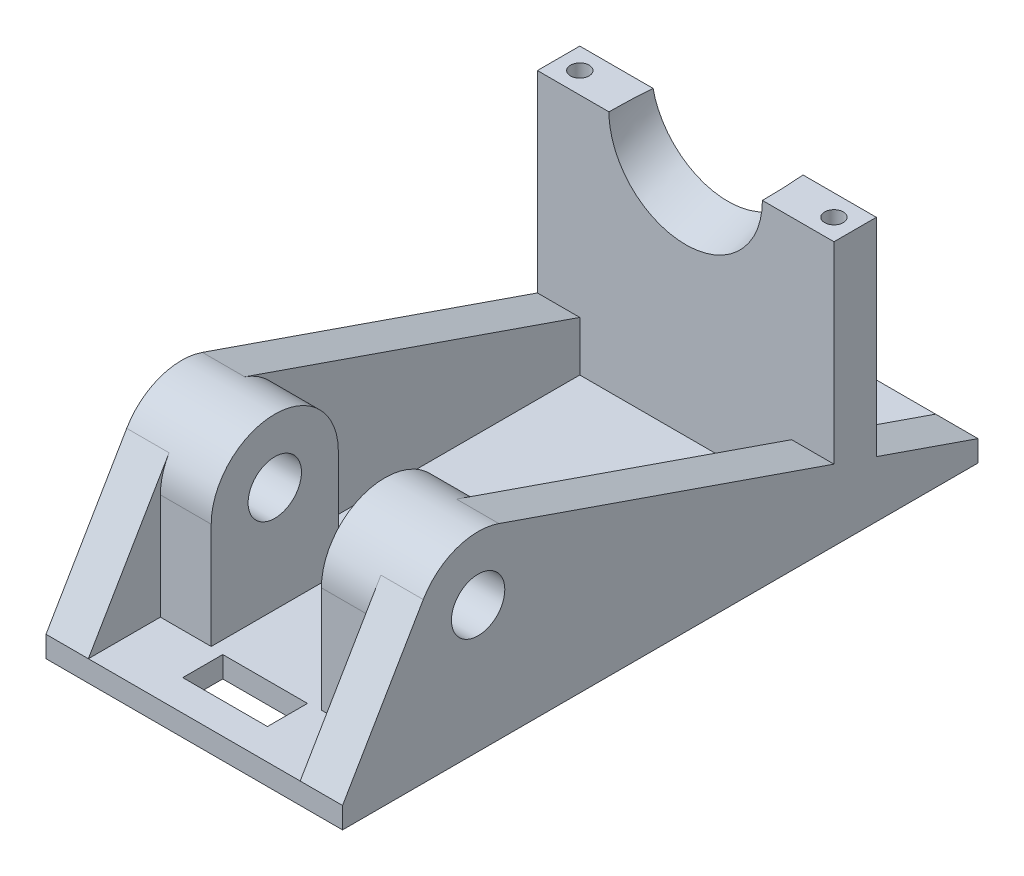
SolidWorks part; units mm, degrees
ref_plane "Front Plane" through (0, 0, 0) normal (0, 0, 1) x (1, 0, 0)
ref_plane "Top Plane" through (0, 0, 0) normal (0, 1, 0) x (1, 0, 0)
ref_plane "Right Plane" through (0, 0, 0) normal (1, 0, 0) x (0, 0, -1)
sketch "Sketch1" plane through (0, 0, 0) normal (0, 1, 0) x (1, 0, 0)
  line L1 (22.225, -47.625) -> (-22.225, -47.625)
  line L2 (22.225, -47.625) -> (22.225, 47.625)
  line L3 (22.225, 47.625) -> (-22.225, 47.625)
  line L4 (-22.225, -47.625) -> (-22.225, 47.625)
  line L5 (22.225, -47.625) -> (-22.225, 47.625) construction
  line L6 (22.225, 47.625) -> (-22.225, -47.625) construction
  point P0 (0, 0)
  dimension "D1" = 95.25
  dimension "D2" = 44.45
extrude "Boss-Extrude1" add sketch "Sketch1" along normal blind 3.175
sketch "Sketch2" plane through (0, 0, 0) normal (1, 0, 0) x (0, 0, -1)
  line L3 (-47.625, 3.175) -> (-47.625, 0) construction
  line L4 (-36.83, 3.175) -> (-36.83, 19.05)
  line L5 (-24.1873, 28.0503) -> (47.625, 3.175)
  line L6 (-47.625, 3.175) -> (47.625, 3.175)
  line L7 (-47.625, 3.175) -> (-35.5269, 23.859)
  line L8 (-17.78, 3.175) -> (-17.78, 19.05)
  circle A0 centre (-27.305, 19.05) radius 4
  arc A2 (-35.5269, 23.859) -> (-24.1873, 28.0503) centre (-27.305, 19.05) cw
  arc A3 (-17.78, 19.05) -> (-36.83, 19.05) centre (-27.305, 19.05) ccw
  point P6 (-47.625, 1.5875)
  dimension "D1" = 8
  dimension "D6" = 19.05
  dimension "D2" = 20.32
  dimension "D3" = 19.05
extrude "Boss-Extrude2" add sketch "Sketch2" along normal mid plane 44.45 contours A2 L6 L5 | A2 A0 | A3 L7 L6 L4 region at (0, 9.3974, 40.4061) region at (0, 14.4275, 27.305) region at (0, 10.8864, -3.7601)
extrude "Cut-Extrude1" cut sketch "Sketch2<3>" against normal mid plane 31.75 contours A3 L7 L6 L4 | A3 L8 L6 L5 region at (0, 9.3974, 40.4061) region at (0, 10.8864, -3.7601)
sketch "Sketch2<3>" plane through (0, 0, 0) normal (1, 0, 0) x (0, 0, -1) same geometry as "Sketch2"
extrude "Cut-Extrude2" cut sketch "Sketch2<4>" against normal mid plane 16.51 contours A2 A0 | A0 region at (0, 14.4275, 27.305) region at (0, 19.05, 27.305)
sketch "Sketch2<4>" plane through (0, 0, 0) normal (1, 0, 0) x (0, 0, -1) same geometry as "Sketch2"
sketch "Sketch3" plane through (0, 3.175, 0) normal (0, 1, 0) x (1, 0, 0)
  line L0 (-15.875, 0) -> (15.875, 0) construction
  line L5 (-15.875, -24.1873) -> (-15.875, 47.625) construction
  line L6 (15.875, -17.78) -> (15.875, 47.625) construction
  line L8 (-6.35, 43.005) -> (6.35, 43.005)
  line L9 (-6.35, 43.005) -> (-6.35, 37.005)
  line L10 (-6.35, 37.005) -> (6.35, 37.005)
  line L11 (6.35, 43.005) -> (6.35, 37.005)
  line L12 (-6.35, 43.005) -> (6.35, 37.005) construction
  line L13 (6.35, 43.005) -> (-6.35, 37.005) construction
  line L14 (-15.875, 47.625) -> (15.875, 47.625) construction
  line L15 (-6.35, -37.005) -> (6.35, -37.005)
  line L16 (6.35, -43.005) -> (6.35, -37.005)
  line L17 (-6.35, -43.005) -> (6.35, -43.005)
  line L18 (-6.35, -43.005) -> (-6.35, -37.005)
  point P11 (0, 37.005)
  point P12 (0, 40.005)
  dimension "D1" = 12.7
  dimension "D2" = 6
  dimension "D3" = 7.62
extrude "Cut-Extrude3" cut sketch "Sketch3" against normal through all
sketch "Sketch4" plane through (0, 3.175, 0) normal (0, 1, 0) x (1, 0, 0)
  line L0 (-22.225, -24.1873) -> (-22.225, 47.625) construction
  line L1 (-22.225, 32.385) -> (22.225, 32.385)
  line L2 (-22.225, 32.385) -> (-22.225, 26.035)
  line L3 (-22.225, 26.035) -> (22.225, 26.035)
  line L4 (22.225, 32.385) -> (22.225, 26.035)
  line L5 (22.225, -24.1873) -> (22.225, 47.625) construction
  line L6 (-6.35, 43.005) -> (-6.35, 37.005) construction
  point P10 (-6.35, 40.005)
  dimension "D1" = 7.62
  dimension "D2" = 6.35
extrude "Boss-Extrude3" add sketch "Sketch4" along normal blind 55.88
ref_plane "Plane1" through (0, 0, 0) normal (1, 0, 0) x (0, 0, -1)
sketch "Sketch5" plane through (0, 0, 0) normal (1, 0, 0) x (0, 0, -1)
  line L0 (-27.305, 19.05) -> (48.895, 19.05) construction
  line L1 (-27.305, 19.05) -> (43.8338, 46.3576)
  dimension "D1" = 76.2
  dimension "D2" = 76.2
  dimension "D3" = 21
sketch "Sketch6" plane through (0, 0, -26.035) normal (0, 0, 1) x (1, 0, 0)
  circle A0 centre (0, 39.5253) radius 11.5
  point P0 (0, 39.5253)
  point P1 (0, 0)
  dimension "D1" = 23
sweep "Cut-Sweep1" cut profiles "Sketch6" path "Sketch5"
sketch "Sketch10" plane through (0, 0, -26.035) normal (0, 0, 1) x (1, 0, 0)
  line L1 (-22.225, 59.055) -> (-22.225, 10.6536) construction
  line L2 (22.225, 59.055) -> (22.225, 10.6536) construction
  line L4 (-22.225, 39.5253) -> (-15.31, 39.5253)
  line L5 (15.31, 39.5253) -> (22.225, 39.5253)
  line L6 (-22.225, 39.5253) -> (-22.225, 59.055)
  line L7 (-22.225, 59.055) -> (22.225, 59.055)
  line L8 (22.225, 59.055) -> (22.225, 39.5253)
  circle A3 centre (0, 39.5253) radius 11.5 construction
  arc A4 (15.31, 39.5253) -> (-15.31, 39.5253) centre (0, 39.5253) ccw
  dimension "D2" = 3.81
sweep "Cut-Sweep4" cut profiles "Sketch10" path "Sketch5<4>"
sketch "Sketch5<4>" plane through (0, 0, 0) normal (1, 0, 0) x (0, 0, -1) same geometry as "Sketch5"
sketch "Sketch11" plane through (0, 0, -26.035) normal (0, 0, 1) x (1, 0, 0)
  line L0 (22.225, 39.5253) -> (22.225, 10.6536) construction
  line L1 (-22.225, 39.5253) -> (22.225, 39.5253)
  line L2 (-22.225, 39.5253) -> (-22.225, 47.1453)
  line L3 (-22.225, 47.1453) -> (22.225, 47.1453)
  line L4 (22.225, 39.5253) -> (22.225, 47.1453)
  arc A0 (15.31, 39.5253) -> (13.279, 47.1453) centre (0, 39.5253) ccw
  arc A1 (-13.279, 47.1453) -> (-15.31, 39.5253) centre (0, 39.5253) ccw
  line M6 (-15.31, 39.5253) -> (-22.225, 39.5253)
  line M14 (22.225, 39.5253) -> (15.31, 39.5253)
  arc M15 (15.31, 39.5253) -> (-15.31, 39.5253) centre (0, 39.5253) ccw
  dimension "D1" = 7.62
extrude "Boss-Extrude4" add sketch "Sketch11" against normal blind 6.35 contours L3 L2 M6 M15 | L4 L3 M14 M15 region at (-18.4148, 43.5031, -26.035) region at (18.4148, 43.5031, -26.035)
sketch "Sketch12" plane through (0, 47.1453, 0) normal (0, 1, 0) x (1, 0, 0)
  line L0 (-22.225, 32.385) -> (-22.225, 26.035) construction
  line L1 (-22.225, 32.385) -> (-15.875, 32.385) construction
  line L2 (0, 0) -> (0, 50.8)
  circle A0 centre (-19.05, 29.21) radius 1.4
  circle A1 centre (19.05, 29.21) radius 1.4
  dimension "D3" = 2.8
  dimension "D1" = 3.175
  dimension "D2" = 3.175
  dimension "D4" = 50.8
extrude "Cut-Extrude4" cut sketch "Sketch12" against normal blind 18.75 contours A0 | A1 region at (-19.05, 47.1453, -29.21) region at (19.05, 47.1453, -29.21)
chamfer "Chamfer1" distance 4.83 distance2 4.32 2 edges at (19.05, 47.1453, -27.81) (-19.05, 47.1453, -27.81) first distance on face at (19.05, 28.3953, -27.81) first distance on face at (-19.05, 47.1453, -27.81)
sketch "Sketch13" plane through (0, 0, -26.035) normal (0, 0, 1) x (1, 0, 0)
  line L1 (-27.9424, 39.5253) -> (29.3265, 39.5253)
  line L2 (-27.9424, 39.5253) -> (-27.9424, 59.1987)
  line L3 (-27.9424, 59.1987) -> (29.3265, 59.1987)
  line L4 (29.3265, 39.5253) -> (29.3265, 59.1987)
extrude "Cut-Extrude5" cut sketch "Sketch13" against normal through all both and the other way through all
